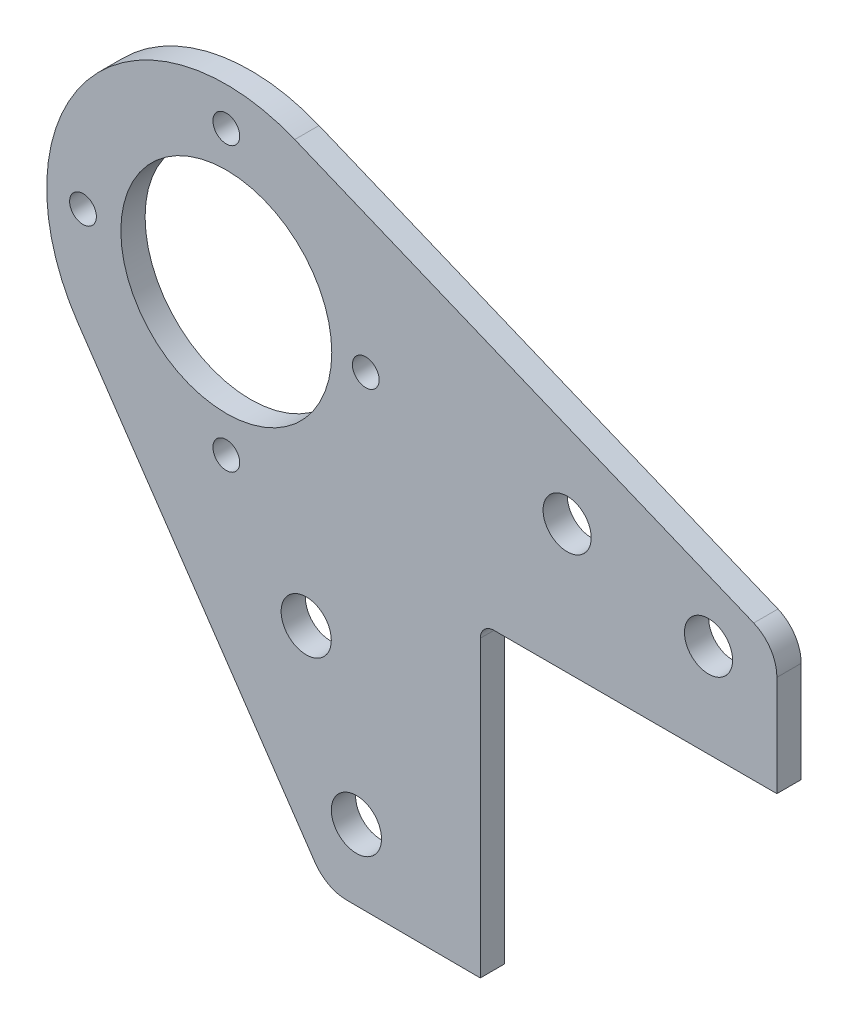
SolidWorks part; units mm, degrees
ref_plane "Front Plane" through (0, 0, 0) normal (0, 0, 1) x (1, 0, 0)
ref_plane "Top Plane" through (0, 0, 0) normal (0, 1, 0) x (1, 0, 0)
ref_plane "Right Plane" through (0, 0, 0) normal (1, 0, 0) x (0, 0, -1)
sketch "Sketch1" plane through (0, 0, 0) normal (0, 0, 1) x (1, 0, 0)
  line L0 (38.9707, 0.452) -> (56.4763, 0.3642)
  line L1 (56.4763, 0.3642) -> (56.4763, 38.8647)
  line L2 (58.2853, 40.6556) -> (95.2858, 40.6556)
  line L3 (95.2858, 40.6556) -> (95.2858, 53.8356)
  line L4 (92.2575, 58.4832) -> (32.2026, 83.2389)
  line L5 (3.8138, 48.2982) -> (34.8611, 2.6404)
  line L6 (4.4934, 61.5125) -> (41.4929, 61.5125) construction
  line L7 (23.2466, 80.0122) -> (23.2466, 43.0127) construction
  arc A0 (34.8611, 2.6404) -> (38.9707, 0.452) centre (38.9957, 5.4519) ccw
  arc A1 (58.2853, 40.6556) -> (56.4763, 38.8647) centre (58.2763, 38.8556) ccw
  arc A2 (95.2858, 53.8356) -> (92.2575, 58.4832) centre (90.2861, 53.8882) ccw
  arc A3 (32.2026, 83.2389) -> (3.8138, 48.2982) centre (23.2466, 61.5125) ccw
  circle A4 centre (23.2466, 43.0127) radius 1.75
  circle A5 centre (4.4934, 61.5125) radius 1.75
  circle A6 centre (23.2466, 80.0122) radius 1.75
  circle A7 centre (41.4929, 61.5125) radius 1.75
  circle A9 centre (23.2466, 61.5125) radius 13.8
  point P19 (23.2466, 61.5125)
base flange "Base-Flange1" sketch "Sketch1" thickness 3.175 reverse thickness direction no parameters "D1"=3.175
sketch "Sketch5" plane through (0, 0, -3.175) normal (0, 0, -1) x (-1, 0, 0)
  circle A0 centre (-23.2466, 61.5125) radius 13.8 construction
  circle A1 centre (-23.2466, 61.5125) radius 13.8
sketch "Sketch6" plane through (0, 0, 0) normal (0, 0, 1) x (1, 0, 0)
  line L1 (39.2241, 0.0868) -> (56.5368, 0)
  line L2 (56.5368, 0) -> (56.7297, 38.4995)
  line L3 (58.5387, 40.2904) -> (95.5383, 40.105)
  line L4 (95.5383, 40.105) -> (95.6053, 53.4703)
  line L5 (92.5109, 58.118) -> (32.456, 82.8737)
  line L6 (4.0672, 47.933) -> (35.1145, 2.2752)
  arc A0 (35.1145, 2.2752) -> (39.2241, 0.0868) centre (39.2491, 5.0867) ccw
  arc A1 (58.5387, 40.2904) -> (56.7297, 38.4995) centre (58.5297, 38.4904) ccw
  arc A2 (95.6053, 53.4703) -> (92.5109, 58.118) centre (90.6053, 53.4953) ccw
  arc A3 (32.456, 82.8737) -> (4.0672, 47.933) centre (23.5, 61.1472) ccw
  circle A4 centre (40.2698, 9.6679) radius 3.2825
  circle A5 centre (33.7012, 28.8843) radius 3.2825
  circle A6 centre (86.3418, 52.8877) radius 3.15
  circle A7 centre (67.8437, 57.5027) radius 3.15
  point P1 (47.8804, 0.0434)
extrude "Cut-Extrude1" cut sketch "Sketch6" against normal through all contours A6 | A4 | A5 | A7 normal cut yes
sketch "Bend-Lines1" [suppressed] plane through (0, 0, 0) normal (0, 1, 0) x (1, 0, 0)
sketch "Bounding-Box1" [suppressed] plane through (0, 0, 0) normal (0, 1, 0) x (1, 0, 0)
sheet metal parameters "Sheet-Metal1" thickness 3.175 parameters "D1"=3.175
flat pattern "Flat-Pattern1" [suppressed]
sketch "Bend-Lines2" plane through (0, 0, 0) normal (0, 1, 0) x (1, 0, 0)
sketch3d "Bounding-Box2" [suppressed]
  line L0 (-0.3181, 105.6356, 0) -> (64.0699, 43.0191, 0) construction
  line L1 (-56.4466, 47.9191, 0) -> (7.9414, -14.6974, 0) construction
  line L2 (-0.3181, 105.6356, 0) -> (-56.4466, 47.9191, 0) construction
  line L3 (64.0699, 43.0191, 0) -> (7.9414, -14.6974, 0) construction
sketch "Sketch5-1" plane through (0, 0, -3.175) normal (0, 0, -1) x (-1, 0, 0)
  circle A1 centre (-23.2466, 61.5125) radius 13.8
sheet metal parameters "Sheet-Metal5" thickness 3.175 parameters "D1"=3.175
flat pattern "Flat-Pattern1" [suppressed]
sketch "Bend-Lines2" plane through (0, 0, 0) normal (0, 1, 0) x (1, 0, 0)
sketch3d "Bounding-Box2" [suppressed]
  line L0 (-0.7511, 105.5058, 0) -> (63.9641, 43.1708, 0) construction
  line L1 (-56.5741, 47.5512, 0) -> (8.1411, -14.7838, 0) construction
  line L2 (-0.7511, 105.5058, 0) -> (-56.5741, 47.5512, 0) construction
  line L3 (63.9641, 43.1708, 0) -> (8.1411, -14.7838, 0) construction
sketch "Sketch5-1" [suppressed] plane through (0, 0, -3.175) normal (0, 0, -1) x (-1, 0, 0)
  circle A1 centre (-23.2466, 61.5125) radius 13.8
